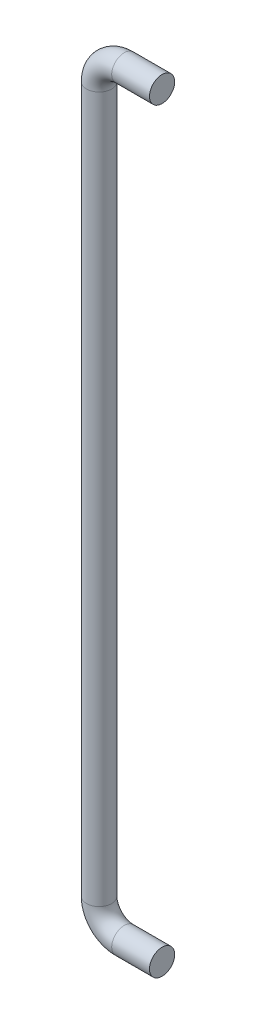
SolidWorks part; units mm, degrees
ref_plane "Ebene vorne" through (0, 0, 0) normal (0, 0, 1) x (1, 0, 0)
ref_plane "Ebene oben" through (0, 0, 0) normal (0, 1, 0) x (1, 0, 0)
ref_plane "Ebene rechts" through (0, 0, 0) normal (1, 0, 0) x (0, 0, -1)
sketch "Skizze1" plane through (0, 0, 0) normal (0, 0, 1) x (1, 0, 0)
  line L1 (-5, 300) -> (25, 300)
  line L2 (-25, 280) -> (-25, -280)
  line L3 (-5, -300) -> (25, -300)
  line L4 (25, 300) -> (25, -300) construction
  line L5 (-25, 300) -> (25, -300) construction
  line L6 (-25, -300) -> (25, 300) construction
  arc A0 (-5, -300) -> (-25, -280) centre (-5, -280) cw
  arc A1 (-25, 280) -> (-5, 300) centre (-5, 280) cw
  point P0 (0, 0)
  dimension "D3" = 20
  dimension "D1" = 600
  dimension "D2" = 50
ref_plane "Ebene1" through (25, 0, 0) normal (1, 0, 0) x (0, 0, -1)
sketch "Skizze2" plane through (25, 0, 0) normal (1, 0, 0) x (0, 0, -1)
  line L0 (0, -300) -> (0, 300) construction
  line L1 (0, 300) -> (0, 280) construction
  circle A0 centre (0, 300) radius 10
sweep "Austragung1" add profiles "Skizze2" path "Skizze1"
ref_axis "Achse1" through (-178.4434, 300, 0) along (1, 0, 0)
ref_axis "Achse2" through (315.8669, -300, 0) along (-1, 0, 0)
